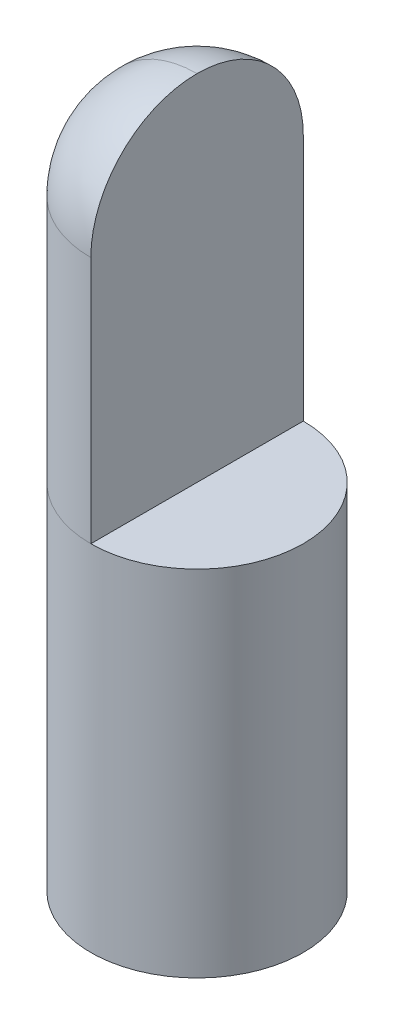
SolidWorks part; units mm, degrees
ref_plane "Спереди" through (0, 0, 0) normal (0, 0, 1) x (1, 0, 0)
ref_plane "Сверху" through (0, 0, 0) normal (0, 1, 0) x (1, 0, 0)
ref_plane "Сбоку" through (0, 0, 0) normal (1, 0, 0) x (0, 0, -1)
sketch "Эскиз1" plane through (0, 0, 0) normal (0, 0, 1) x (1, 0, 0)
  line L1 (0, 0) -> (-30, 0)
  line L2 (0, 0) -> (0, 100)
  line L3 (0, 100) -> (-30, 100)
  line L4 (-30, 0) -> (-30, 100)
  dimension "D1" = 100
  dimension "D2" = 30
revolve "Повернуть1" add sketch "Эскиз1" angle 360 about L2
sketch "Эскиз2" plane through (0, 100, 0) normal (0, 1, 0) x (1, 0, 0)
  line L1 (0, -30) -> (-30, -30)
  line L2 (0, -30) -> (0, 30)
  line L3 (0, 30) -> (-30, 30)
  line L4 (-30, -30) -> (-30, 30)
  dimension "D1" = 60
  dimension "D2" = 30
extrude "Бобышка-Вытянуть1" add sketch "Эскиз2" along normal blind 100
fillet "Скругление1" radius 30 2 edges at (-30, 150, -30) (-30, 150, 30)
